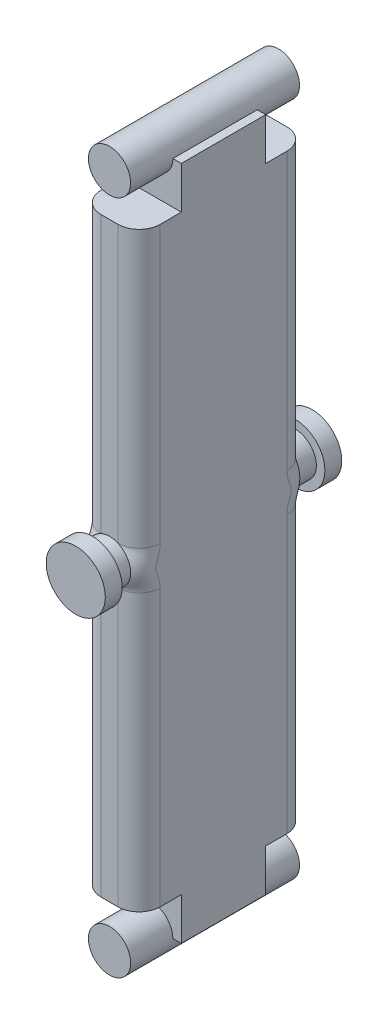
SolidWorks part; units mm, degrees
ref_plane "Front Plane" through (0, 0, 0) normal (0, 0, 1) x (1, 0, 0)
ref_plane "Top Plane" through (0, 0, 0) normal (0, 1, 0) x (1, 0, 0)
ref_plane "Right Plane" through (0, 0, 0) normal (1, 0, 0) x (0, 0, -1)
sketch "Sketch1" plane through (0, 0, 0) normal (0, 1, 0) x (1, 0, 0)
  line L1 (0, -20) -> (-14, -20)
  line L2 (0, -20) -> (0, 20)
  line L3 (0, 20) -> (-14, 20)
  line L4 (-14, -20) -> (-14, 20)
  dimension "D1" = 40
  dimension "D2" = 14
  dimension "D3" = 20
extrude "Boss-Extrude1" add sketch "Sketch1" along normal blind 140
sketch "Sketch5" plane through (0, 140, 0) normal (0, 1, 0) x (1, 0, 0)
  line L0 (0, -20) -> (0, 20) construction
  line L1 (0, 10) -> (-14, 10)
  line L2 (0, 10) -> (0, -10)
  line L3 (0, -10) -> (-14, -10)
  line L4 (-14, 10) -> (-14, -10)
  line L5 (-14, 20) -> (-14, -20) construction
  dimension "D1" = 20
  dimension "D2" = 10
extrude "Boss-Extrude5" add sketch "Sketch5" along normal blind 10
sketch "Sketch6" plane through (0, 0, 0) normal (0, 0, 1) x (1, 0, 0)
  line L0 (-14, 150) -> (0, 150) construction
  circle A0 centre (-7, 150) radius 5
  dimension "D1" = 10
extrude "Boss-Extrude6" add sketch "Sketch6" along normal blind 20 and the other way blind 20
sketch "Sketch7" plane through (0, 0, 20) normal (0, 0, 1) x (1, 0, 0)
  circle A0 centre (-7, 70) radius 5
  dimension "D1" = 10
extrude "Boss-Extrude7" add sketch "Sketch7" along normal blind 4
sketch "Sketch8" plane through (0, 0, 24) normal (0, 0, 1) x (1, 0, 0)
  circle A0 centre (-7, 70) radius 7
  dimension "D1" = 14
extrude "Boss-Extrude8" add sketch "Sketch8" along normal blind 4
mirror "Mirror1" about plane through (0, 0, 0) normal (0, 0, 1) of "Boss-Extrude8", "Boss-Extrude7"
sketch "Sketch9" plane through (0, 0, 0) normal (0, -1, 0) x (1, 0, 0)
  line L0 (-14, -20) -> (-14, 20) construction
  line L1 (-14, 10) -> (0, 10)
  line L2 (-14, 10) -> (-14, -10)
  line L3 (-14, -10) -> (0, -10)
  line L4 (0, 10) -> (0, -10)
  line L5 (0, 20) -> (0, -20) construction
  dimension "D1" = 20
  dimension "D2" = 10
extrude "Boss-Extrude9" add sketch "Sketch9" along normal blind 10
sketch "Sketch10" plane through (0, 0, 0) normal (0, 0, 1) x (1, 0, 0)
  line L0 (0, -10) -> (-14, -10) construction
  circle A0 centre (-7, -10) radius 5
  dimension "D1" = 10
extrude "Boss-Extrude10" add sketch "Sketch10" along normal blind 20 and the other way blind 20
fillet "Fillet1" radius 5 4 edges at (0, 70, 20) (0, 70, -20) (-14, 70, 20) (-14, 70, -20)
